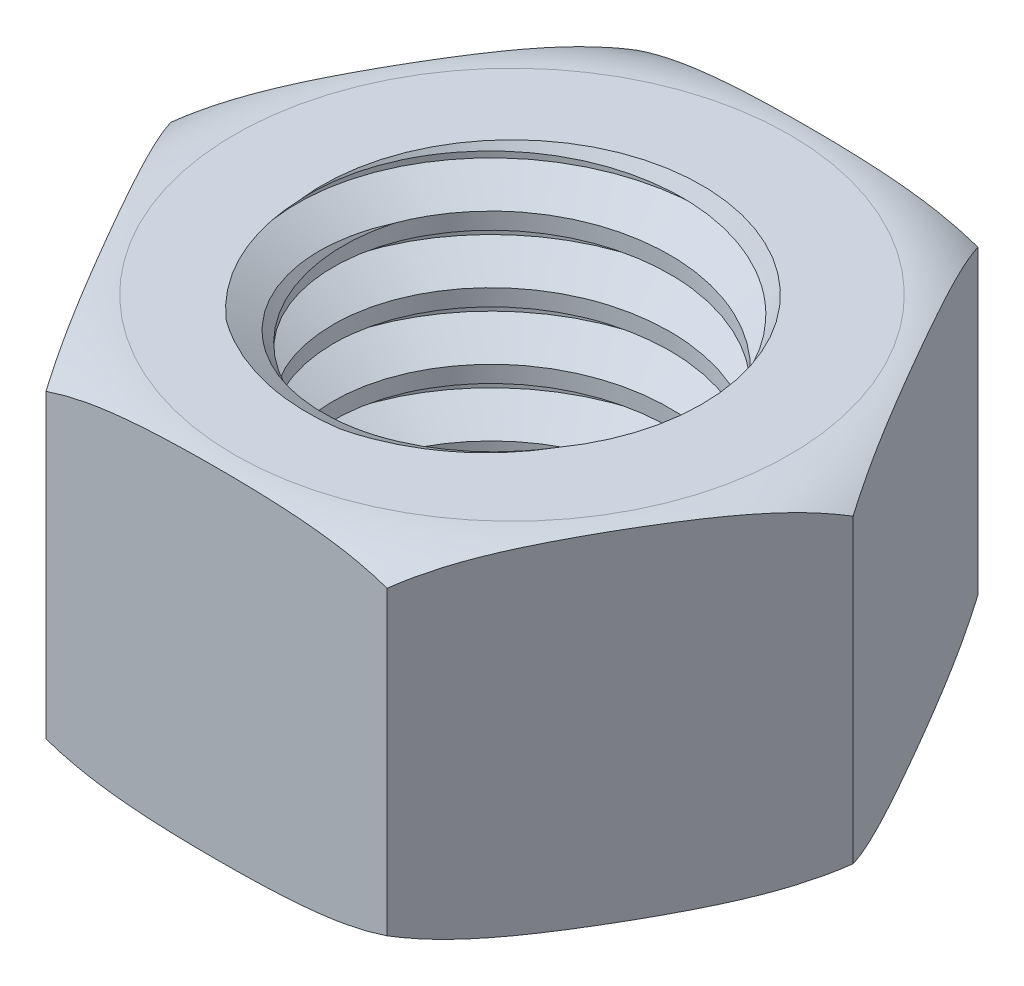
SolidWorks part; units mm, degrees
ref_plane "Front Plane" through (0, 0, 0) normal (0, 0, 1) x (1, 0, 0)
ref_plane "Top Plane" through (0, 0, 0) normal (0, 1, 0) x (1, 0, 0)
ref_plane "Right Plane" through (0, 0, 0) normal (1, 0, 0) x (0, 0, -1)
sketch "Sketch1" plane through (0, 0, 0) normal (0, 1, 0) x (1, 0, 0)
  line L1 (8.1609, 0) -> (4.0805, 7.0676)
  line L2 (4.0805, 7.0676) -> (-4.0805, 7.0675)
  line L3 (-4.0805, 7.0675) -> (-8.1609, 0)
  line L4 (-8.1609, 0) -> (-4.0805, -7.0676)
  line L5 (-4.0805, -7.0676) -> (4.0805, -7.0675)
  line L6 (4.0805, -7.0675) -> (8.1609, 0)
  circle A0 centre (0, 0) radius 7.0676 construction
  circle A1 centre (0, 0) radius 4.0323
  dimension "D2" = 8.0645
  dimension "D1" = 14.1351
extrude "Boss-Extrude1" add sketch "Sketch1" along normal mid plane 8.2169
sketch "Sketch2" plane through (0, 0, 0) normal (0, 0, 1) x (1, 0, 0)
  line L0 (8.1609, 4.1084) -> (6.6369, 4.1084)
  line L1 (4.0805, 4.1084) -> (8.1609, 4.1084) construction
  line L2 (8.1609, 4.1084) -> (8.1609, 3.6004)
  line L3 (8.1609, 4.1084) -> (8.1609, -4.1084) construction
  line L4 (0, 4.1084) -> (0, -4.9515) construction
  line L5 (-9.1682, 0) -> (11.477, 0) construction
  line L6 (8.1609, -4.1084) -> (8.1609, -3.6004)
  line L7 (8.1609, -4.1084) -> (6.6369, -4.1084)
  arc A1 (6.6369, 4.1084) -> (8.1609, 3.6004) centre (6.5376, 1.2704) cw
  arc A2 (6.6369, -4.1084) -> (8.1609, -3.6004) centre (6.5376, -1.2704) ccw
  dimension "D1" = 1.524
  dimension "D2" = 0.508
revolve "Cut-Revolve2" cut sketch "Sketch2" angle 360 about L4
chamfer "Chamfer2" distance 0.508 angle 63 2 edges at (0, -4.1084, 4.0323) (0, 4.1084, 4.0323) first distance on face at (0, 4.1084, 4.0323)
thread "Thread2" pitch 1.5875 method cut profile "Thread Profile2" start angle 0, offset 3.54, length 15.08, pitch 1.5875, diameter 8.0645
ref_plane "Plane2" through (4.0323, -7.1404, 0) normal (0, 0, 1) x (1, 0, 0)
sketch "Thread Profile2" plane through (4.0323, -7.1404, 0) normal (0, 0, 1) x (1, 0, 0)
  line L0 (0, 0) -> (0, 1.5875) construction
  line L1 (0, 0) -> (0.8593, 0.4961)
  line L2 (0.8593, 0.4961) -> (0.8593, 0.6945)
  line L3 (0.8593, 0.6945) -> (0, 1.1906)
  line L4 (0.8593, 0.5953) -> (0, 0.5953) construction
  line L11 (0, 0) -> (0, 1.1906)
  point P2 (0, 0)
  dimension "Pitch" = 1.5875
  dimension "Profile_Angle" = 60
  dimension "Profile_Land" = 0.1984
  dimension "Profile_Height" = 0.8593
